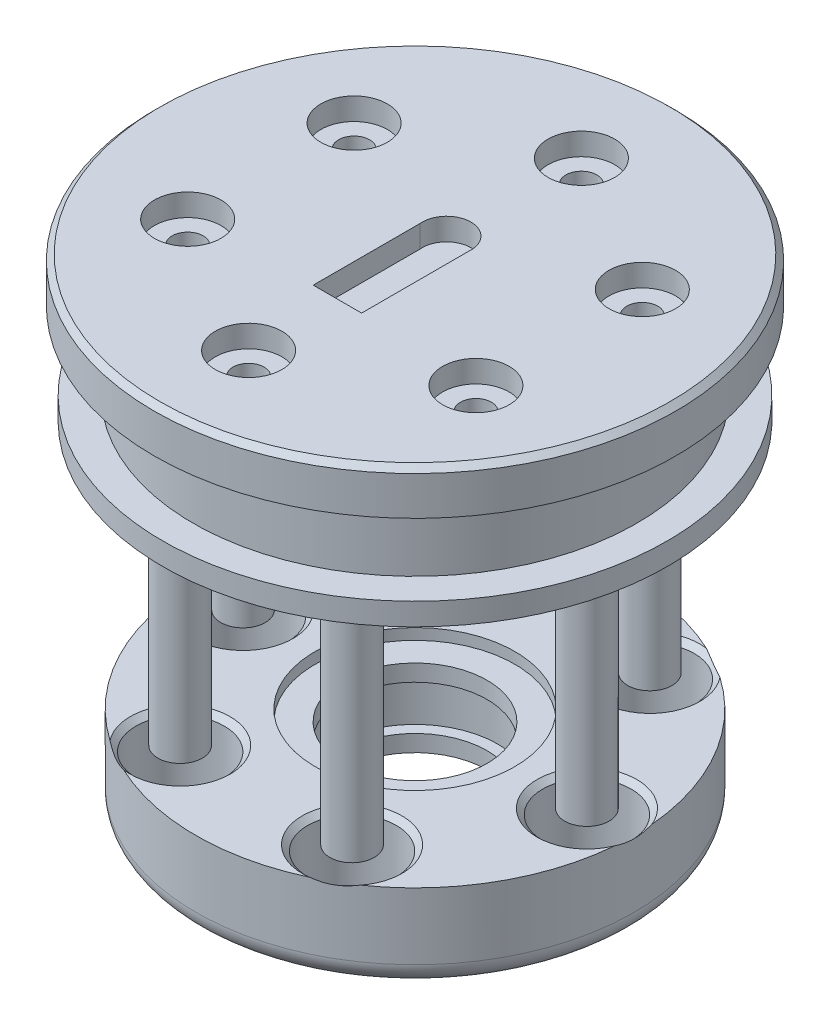
SolidWorks part; units mm, degrees
note: The reader was unsure of these and kept them because the rebuilt part matched: shared geometry of "Sketch4<2>", "Sketch14<4>".
ref_plane "Front" through (0, 0, 0) normal (0, 0, 1) x (1, 0, 0)
ref_plane "Top" through (0, 0, 0) normal (0, 1, 0) x (1, 0, 0)
ref_plane "Right" through (0, 0, 0) normal (1, 0, 0) x (0, 0, -1)
sketch "Sketch1" plane through (0, 0, 0) normal (0, 1, 0) x (1, 0, 0)
  line L0 (0, 0) -> (15.5, 0) construction
  circle A0 centre (15.5, 0) radius 2
  circle A1 centre (7.75, -13.4234) radius 2
  circle A2 centre (-7.75, -13.4234) radius 2
  circle A3 centre (-15.5, 0) radius 2
  circle A4 centre (-7.75, 13.4234) radius 2
  circle A5 centre (7.75, 13.4234) radius 2
  dimension "D2" = 4
  dimension "D1" = 15.5
extrude "Boss-Extrude1" add sketch "Sketch1" along normal blind 22.5
sketch "Sketch2" plane through (0, 0, 0) normal (0, -1, 0) x (1, 0, 0)
  circle A0 centre (0, 0) radius 7.5
  circle A1 centre (15.5, 0) radius 4 construction
  circle A2 centre (0, 0) radius 19.75
  dimension "D1" = 8
  dimension "D2" = 15
  dimension "D3" = 39.5
extrude "Boss-Extrude2" add sketch "Sketch2" along normal blind 8
sketch "Sketch4" plane through (0, 0, 0) normal (0, 1, 0) x (1, 0, 0)
  circle A0 centre (0, 0) radius 6.5
  circle A1 centre (0, 0) radius 7.5 construction
  circle A2 centre (0, 0) radius 7.5
  dimension "D1" = 13
extrude "Boss-Extrude3" add sketch "Sketch4" against normal blind 2.5
extrude "Boss-Extrude4" add sketch "Sketch4<2>" along normal blind 1.5 from surface at -8 starting at face at (0, -8, -19.75)
sketch "Sketch4<2>" plane through (0, 0, 0) normal (0, 1, 0) x (1, 0, 0) same geometry as "Sketch4"
sketch "Sketch5" plane through (0, 0, 0) normal (0, 1, 0) x (1, 0, 0)
  circle A0 centre (0, 0) radius 9
  dimension "D1" = 18
extrude "Cut-Extrude1" cut sketch "Sketch5" against normal blind 1
sketch "Sketch6" plane through (0, 22.5, 0) normal (0, 1, 0) x (1, 0, 0)
  circle A0 centre (0, 0) radius 20
  circle A1 centre (15.5, 0) radius 4 construction
  dimension "D1" = 8
  dimension "D2" = 40
extrude "Boss-Extrude5" add sketch "Sketch6" along normal blind 9
sketch "Sketch10" plane through (0, 22.5, 0) normal (0, -1, 0) x (1, 0, 0)
  circle A0 centre (0, 0) radius 22.75
  dimension "D1" = 45.5
extrude "Boss-Extrude7" add sketch "Sketch10" against normal blind 2
sketch "Sketch8" plane through (0, 22.5, 0) normal (0, -1, 0) x (1, 0, 0)
  circle A0 centre (0, 0) radius 7.5
  dimension "D1" = 15
extrude "Cut-Extrude2" cut sketch "Sketch8" against normal blind 4
sketch "Sketch9" plane through (0, 26.5, 0) normal (0, -1, 0) x (1, 0, 0)
  circle A0 centre (0, 0) radius 6
  dimension "D1" = 12
extrude "Cut-Extrude3" cut sketch "Sketch9" against normal blind 1.5
sketch "Sketch11" plane through (0, 31.5, 0) normal (0, 1, 0) x (1, 0, 0)
  circle A0 centre (0, 0) radius 23.5
  dimension "D1" = 47
extrude "Boss-Extrude9" add sketch "Sketch11" along normal blind 4 contours A0
fillet "Fillet1" radius 2 1 edges at (0, -8, -19.75)
sketch "Sketch14" plane through (0, 0, 0) normal (0, 1, 0) x (1, 0, 0)
  circle A0 centre (15.5, 0) radius 4
  circle A1 centre (7.75, -13.4234) radius 4
  circle A2 centre (-7.75, -13.4234) radius 4
  circle A3 centre (-15.5, 0) radius 4
  circle A4 centre (-7.75, 13.4234) radius 4
  circle A5 centre (7.75, 13.4234) radius 4
  dimension "D1" = 8
extrude "Cut-Extrude4" cut sketch "Sketch14" against normal blind 6
extrude "Cut-Extrude6" cut sketch "Sketch14<4>" along normal blind 6 from surface at 22.5 starting at face at (0, 22.5, -7.5)
sketch "Sketch14<4>" plane through (0, 0, 0) normal (0, 1, 0) x (1, 0, 0) same geometry as "Sketch14"
chamfer "Chamfer1" distance 0.5 angle 45 6 edges at (15.5, 0, 4) (7.75, 0, 17.4234) (-7.75, 0, 17.4234) (-15.5, 0, 4) (-7.75, 0, -9.4234) (7.75, 0, -9.4234)
chamfer "Chamfer2" distance 0.5 angle 45 6 edges at (-15.5, 22.5, 4) (-7.75, 22.5, -9.4234) (7.75, 22.5, -9.4234) (15.5, 22.5, 4) (7.75, 22.5, 17.4234) (-7.75, 22.5, 17.4234)
sketch "Sketch15" plane through (0, 22.5, 0) normal (0, -1, 0) x (1, 0, 0)
  line L0 (0, 0) -> (12.9904, 7.5) construction
  line L2 (9.7904, 5.6525) -> (12.9904, 3.805)
  line L3 (12.9904, 3.805) -> (16.1904, 5.6525)
  line L4 (16.1904, 5.6525) -> (16.1904, 9.3475)
  line L5 (16.1904, 9.3475) -> (12.9904, 11.195)
  line L6 (12.9904, 11.195) -> (9.7904, 9.3475)
  line L7 (9.7904, 9.3475) -> (9.7904, 5.6525)
  circle A0 centre (12.9904, 7.5) radius 3.2 construction
  circle A1 centre (12.9904, 7.5) radius 1.4 construction
  dimension "D3" = 2.8
  dimension "D1" = 6.4
  dimension "D2" = 30
  dimension "D4" = 15
extrude "Cut-Extrude7" cut sketch "Sketch15" against normal blind 3
sketch "Sketch16" plane through (0, 25.5, 0) normal (0, -1, 0) x (1, 0, 0)
  line L0 (16.1904, 9.3475) -> (9.7904, 5.6525) construction
  circle A0 centre (12.9904, 7.5) radius 1.4
  dimension "D1" = 2.8
extrude "Cut-Extrude8" cut sketch "Sketch16" against normal up to surface (10 mm away) up to face at (0, 35.5, 23.5)
sketch "Sketch17" plane through (0, 35.5, 0) normal (0, 1, 0) x (1, 0, 0)
  circle A0 centre (12.9904, -7.5) radius 3
  dimension "D1" = 6
extrude "Cut-Extrude9" cut sketch "Sketch17" against normal blind 2
pattern_circular "CirPattern1" count 6 over 360 about axis through (0, 0, 0) along (0, 1, 0) of "Cut-Extrude9", "Cut-Extrude7", "Cut-Extrude8"
sketch "Sketch18" plane through (0, 0, 0) normal (0, 0, 1) x (1, 0, 0)
  line L0 (-58.319, 31.5) -> (42.619, 31.5)
  line L1 (-23.5, 31.5) -> (23.5, 31.5) construction
split "Split1" trim tools "Sketch18" bodies to split 134 resulting bodies 135 136
chamfer "Chamfer3" distance 0.5 angle 45 1 edges at (0, 31.5, 20)
sketch "Sketch19" plane through (0, 35.5, 0) normal (0, 1, 0) x (1, 0, 0)
  line L0 (0, 0) -> (0, 2.8475) construction
  line L2 (2.1806, -6.9949) -> (-2.1806, -6.9949)
  line L3 (2.1806, -6.9949) -> (2.1806, 2.6141)
  line L5 (-2.1806, -6.9949) -> (-2.1806, 2.6141)
  line L6 (2.1806, -6.9949) -> (-1.6152, 5.1814) construction
  line L7 (1.6152, 5.1814) -> (-2.1806, -6.9949) construction
  arc A0 (2.1806, 2.6141) -> (-2.1806, 2.6141) centre (0, 2.8475) ccw
extrude "Cut-Extrude10" cut sketch "Sketch19" against normal blind 2
chamfer "Chamfer4" distance 0.5 angle 45 1 edges at (0, 35.5, 23.5)
chamfer "Chamfer5" distance 0.5 angle 45 1 edges at (0, 22.5, -7.5)
